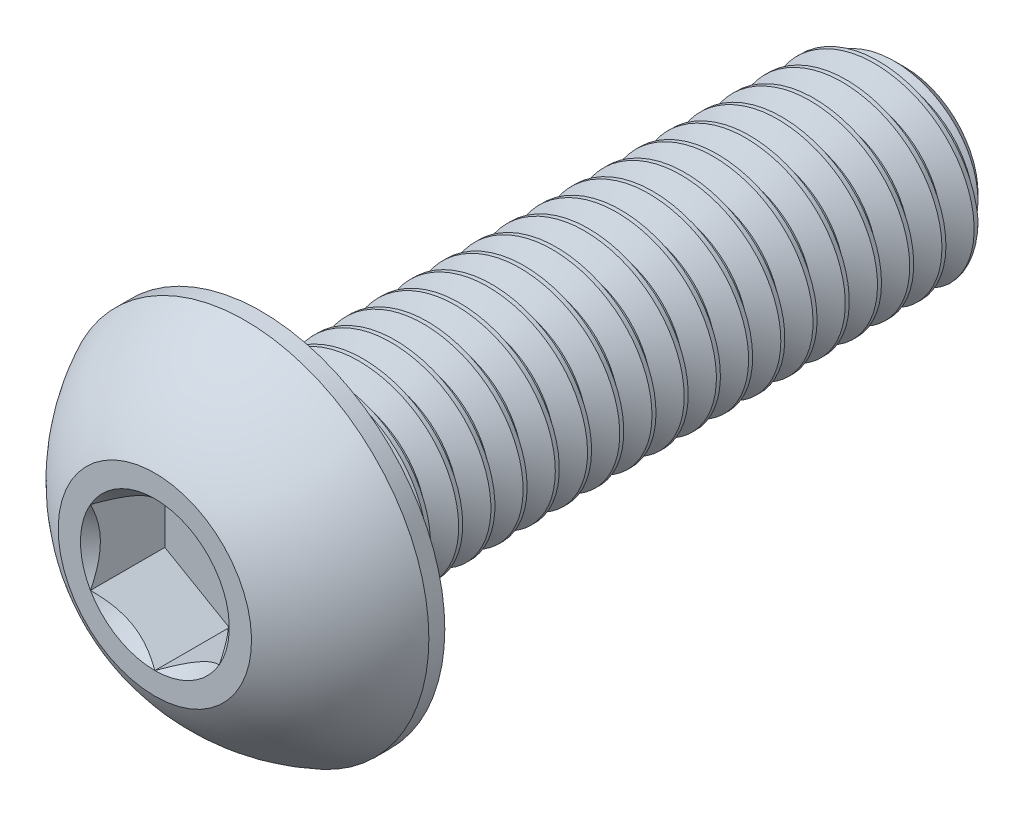
SolidWorks part; units mm, degrees
ref_plane "Front" through (0, 0, 0) normal (0, 0, 1) x (1, 0, 0)
ref_plane "Top" through (0, 0, 0) normal (0, 1, 0) x (1, 0, 0)
ref_plane "Right" through (0, 0, 0) normal (1, 0, 0) x (0, 0, -1)
sketch "Sketch1" plane through (0, 0, 0) normal (1, 0, 0) x (0, 0, -1)
  line L2 (1.65, 1.5) -> (11.65, 1.5)
  line L3 (11.65, 1.5) -> (11.65, 0)
  line L4 (11.65, 0) -> (1.65, 0)
  line L6 (1.4025, 2.85) -> (1.65, 2.85) construction
  line L7 (11.65, 1.5) -> (11.65, -1.5) construction
  line L8 (0, 0) -> (1.65, 0) construction
  line L9 (1.65, 2.85) -> (1.65, -2.85) construction
  line L11 (1.65, 1.5) -> (1.65, 0)
  line L13 (0, 1) -> (0, -1) construction
  line L14 (0, 1) -> (0, 1.5) construction
  arc A3 (0, 1.5) -> (1.4025, 2.85) centre (2.7948, 0) cw construction
  dimension "D1" = 0.2475
  dimension "Head Ht" = 1.65
  dimension "Head Dia" = 5.7
  dimension "Dia" = 3
  dimension "Lg" = 10
  dimension "Hex" = 2
revolve "Revolve1" add sketch "Sketch1" angle 360 mid plane about L4
sketch "Sketch3" plane through (0, 0, -11.65) normal (0, 0, -1) x (-1, 0, 0)
  circle A0 centre (0, 0) radius 1.5
curve "Helix/Spiral1" pitch 0.5 height 10.5 radius 1.5 centre (0, 0, -11.65) axis (0, 0, 1) start towards (0, 1, 0)
sketch "Sketch2" plane through (0, 0, 0) normal (1, 0, 0) x (0, 0, -1)
  line L0 (11.65, 1.5) -> (12.0875, 1.5)
  line L1 (12.0875, 1.5) -> (11.9, 1.1752)
  line L2 (11.9, 1.1752) -> (11.8375, 1.1752)
  line L3 (11.8375, 1.1752) -> (11.65, 1.5)
  line L4 (11.7438, 1.3376) -> (11.9938, 1.3376) construction
  dimension "D1" = 60
  dimension "D2" = 0.0625
  dimension "D3" = 0.25
chamfer "Chamfer1" distance 0.375 angle 45 1 edges at (0, 1.5, -11.65)
sweep "Cut-Sweep1" cut profiles "Sketch2" path "Helix/Spiral1"
sketch "Sketch7" plane through (0, 0, 0) normal (1, 0, 0) x (0, 0, -1)
  line L6 (1.4025, 2.85) -> (1.65, 2.85) construction
  line L8 (0, 0) -> (1.65, 0) construction
  line L11 (1.65, 2.85) -> (1.65, -2.85) construction
  line L12 (1.4025, 2.85) -> (1.65, 2.85)
  line L13 (0, 0) -> (1.65, 0)
  line L14 (0, 1) -> (0, -1) construction
  line L15 (1.65, 2.85) -> (1.65, 0)
  line L16 (0, 1.5) -> (0, 0)
  arc A2 (1.4025, 2.85) -> (0, 1.5) centre (2.7948, 0) ccw construction
  arc A3 (1.4025, 2.85) -> (0, 1.5) centre (2.7948, 0) ccw
revolve "Revolve2" add sketch "Sketch7" angle 360 mid plane about L13
sketch "Sketch5" plane through (0, 0, 0) normal (0, 0, 1) x (1, 0, 0)
  line L1 (1, -0.5774) -> (1, 0.5774)
  line L2 (1, 0.5774) -> (0, 1.1547)
  line L3 (0, 1.1547) -> (-1, 0.5774)
  line L4 (-1, 0.5774) -> (-1, -0.5774)
  line L5 (-1, -0.5774) -> (0, -1.1547)
  line L6 (0, -1.1547) -> (1, -0.5774)
  circle A0 centre (0, 0) radius 1 construction
extrude "Cut-Extrude2" cut sketch "Sketch5" against normal blind 1.155
sketch "Sketch6" plane through (0, 0, 0) normal (0, 0, 1) x (1, 0, 0)
  circle A0 centre (0, 0) radius 1.1547
extrude "Cut-Extrude3" cut sketch "Sketch6" against normal blind 1.155 draft 45
sketch "Sketch9" [suppressed] plane through (0, 0, -4.2164) normal (0, 0, 1) x (1, 0, 0)
  circle A2 centre (0, 0) radius 3.9687
extrude "Boss-Extrude2" [suppressed] add sketch "Sketch9" against normal offset from surface (9.525 mm away) 28.575 up to face at (0, 1.125, -11.65)
sketch "Sketch10" plane through (0, 0, 0) normal (1, 0, 0) x (0, 0, -1)
  line L0 (9.65, 1.5) -> (9.65, -1.5) construction
  point P0 (8.9, -1.5)
  dimension "D1" = 0.75
equation "\"D3@Helix/Spiral1\" = \"Lg@Sketch1\" + \"D4@Helix/Spiral1\""
equation "\"D2@Sketch2\" = \"D4@Helix/Spiral1\" * .125"
equation "\"D3@Sketch2\" = \"D4@Helix/Spiral1\" * .5"
equation "\"D1@Chamfer1\" = \"D4@Helix/Spiral1\" * .75"
equation "\"D1@Cut-Extrude2\" = \"Head Ht@Sketch1\" * .7"
equation "\"D1@Sketch1\" = \"Head Ht@Sketch1\" * .15"
equation "\"D1@Sketch10\" = \"D4@Helix/Spiral1\" * 1.5"
equation "\"D1@Cut-Extrude3\" = \"D1@Cut-Extrude2\""
